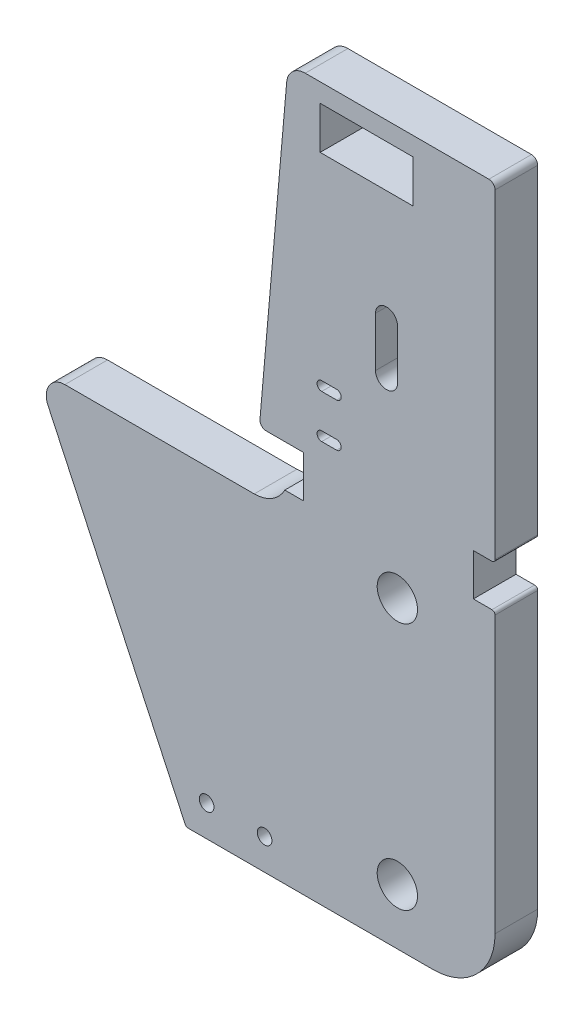
SolidWorks part; units mm, degrees
ref_plane "Front Plane" through (0, 0, 0) normal (0, 0, 1) x (1, 0, 0)
ref_plane "Top Plane" through (0, 0, 0) normal (0, 1, 0) x (1, 0, 0)
ref_plane "Right Plane" through (0, 0, 0) normal (1, 0, 0) x (0, 0, -1)
sketch "Sketch1" plane through (0, 0, 0) normal (0, 0, 1) x (1, 0, 0)
  line L0 (0, 0) -> (0, -53.098)
  line L1 (0, -53.098) -> (-3.5, -53.098)
  line L2 (-3.5, -53.098) -> (-3.5, -59.858)
  line L3 (-3.5, -59.858) -> (0, -59.858)
  line L4 (0, -59.858) -> (0, -114.858)
  line L5 (0, -114.858) -> (-49.8185, -114.858)
  line L6 (-49.8185, -114.858) -> (-74.0665, -62.858)
  line L7 (-33.3545, 0) -> (-38, -53.098)
  line L8 (-38, -53.098) -> (-30.9, -53.098)
  line L9 (-30.9, -53.098) -> (-30.9, -59.858)
  line L10 (-30.9, -59.858) -> (-33.9, -59.858)
  line L11 (-33.9, -59.858) -> (-33.9, -62.858)
  line L12 (-33.9, -62.858) -> (-74.0665, -62.858)
  line L13 (-33.3545, 0) -> (0, 0)
  dimension "D1" = 53.098
  dimension "D2" = 6.76
  dimension "D3" = 3.5
  dimension "D4" = 55
  dimension "D5" = 49.8185
  dimension "D6" = 57.3757
  dimension "D7" = 115
  dimension "D8" = 33.3545
  dimension "D9" = 7.1
  dimension "D10" = 95
  dimension "D11" = 3
  dimension "D12" = 3
extrude "Boss-Extrude1" add sketch "Sketch1" along normal blind 6.88 contours L13 L7 L8 L9 L10 L11 L12 L6 L5 L4 L3 L2 L1 L0
sketch "Sketch2" plane through (0, 0, 6.88) normal (0, 0, 1) x (1, 0, 0)
  line L0 (-33.3545, 0) -> (0, 0) construction
  line L1 (-13.2, -9.858) -> (-28.2, -9.858)
  line L2 (-13.2, -9.858) -> (-13.2, -3)
  line L3 (-13.2, -3) -> (-28.2, -3)
  line L4 (-28.2, -9.858) -> (-28.2, -3)
  line L5 (-13.2, -9.858) -> (-28.2, -3) construction
  line L6 (-13.2, -3) -> (-28.2, -9.858) construction
  line L7 (0, 0) -> (0, -53.098) construction
  point P0 (-20.7, -6.429)
  dimension "D1" = 15
  dimension "D2" = 6.858
  dimension "D3" = 3
  dimension "D4" = 13.2
extrude "Cut-Extrude1" cut sketch "Sketch2" against normal through all
sketch "Sketch3" plane through (0, 0, 6.88) normal (0, 0, 1) x (1, 0, 0)
  line L0 (0, -59.858) -> (0, -114.858) construction
  line L1 (0, -114.858) -> (-49.8185, -114.858) construction
  circle A0 centre (-15.75, -65.858) radius 3.25
  circle A1 centre (-15.75, -105.858) radius 3.25
  dimension "D1" = 6.5
  dimension "D2" = 15.75
  dimension "D3" = 40
  dimension "D4" = 9
extrude "Cut-Extrude2" cut sketch "Sketch3" against normal through all
sketch "Sketch4" plane through (0, 0, 6.88) normal (0, 0, 1) x (1, 0, 0)
  line L0 (0, -59.858) -> (0, -114.858) construction
  line L1 (0, -114.858) -> (-49.8185, -114.858) construction
  line L2 (-27.95, -49.358) -> (-25.55, -49.358) construction
  line L3 (-27.95, -48.608) -> (-25.55, -48.608)
  line L4 (-27.95, -50.108) -> (-25.55, -50.108)
  line L5 (-27.95, -42.358) -> (-25.55, -42.358) construction
  line L6 (-27.95, -41.608) -> (-25.55, -41.608)
  line L7 (-27.95, -43.108) -> (-25.55, -43.108)
  line L8 (-38, -53.098) -> (-30.9, -53.098) construction
  line L9 (0, 0) -> (0, -53.098) construction
  circle A0 centre (-46.5, -109.858) radius 1.1811
  circle A1 centre (-37.1528, -109.858) radius 1.1811
  arc A2 (-27.95, -48.608) -> (-27.95, -50.108) centre (-27.95, -49.358) ccw
  arc A3 (-25.55, -50.108) -> (-25.55, -48.608) centre (-25.55, -49.358) ccw
  arc A4 (-27.95, -41.608) -> (-27.95, -43.108) centre (-27.95, -42.358) ccw
  arc A5 (-25.55, -43.108) -> (-25.55, -41.608) centre (-25.55, -42.358) ccw
  point P10 (-26.75, -49.358)
  point P16 (-26.75, -42.358)
  dimension "D2" = 2.3622
  dimension "D9" = 0.75
  dimension "D1" = 9.3472
  dimension "D3" = 37.1528
  dimension "D4" = 5
  dimension "D5" = 2.4
  dimension "D6" = 3.74
  dimension "D7" = 7
  dimension "D8" = 25.55
extrude "Cut-Extrude3" cut sketch "Sketch4" against normal through all
sketch "Sketch5" plane through (0, 0, 6.88) normal (0, 0, 1) x (1, 0, 0)
  line L0 (-17.5, -27.858) -> (-17.5, -35.858) construction
  line L1 (-15.725, -27.858) -> (-15.725, -35.858)
  line L2 (-19.275, -27.858) -> (-19.275, -35.858)
  line L3 (0, 0) -> (0, -53.098) construction
  line L4 (-33.3545, 0) -> (0, 0) construction
  arc A0 (-15.725, -27.858) -> (-19.275, -27.858) centre (-17.5, -27.858) ccw
  arc A1 (-19.275, -35.858) -> (-15.725, -35.858) centre (-17.5, -35.858) ccw
  point P2 (-17.5, -31.858)
  dimension "D2" = 1.775
  dimension "D1" = 8
  dimension "D3" = 17.5
  dimension "D4" = 27.858
extrude "Cut-Extrude4" cut sketch "Sketch5" against normal through all
fillet "Fillet1" radius 10 1 edges at (0, -114.858, 3.44)
fillet "Fillet2" radius 3 2 edges at (-74.0665, -62.858, 3.44) (-33.3545, 0, 3.44)
fillet "Fillet3" radius 0.5 3 edges at (0, -53.098, 3.44) (0, -59.858, 3.44) (-49.8185, -114.858, 3.44)
fillet "Fillet4" radius 1 2 edges at (0, 0, 3.44) (-38, -53.098, 3.44)
fillet "Fillet5" radius 5.5512 1 edges at (-33.9, -62.858, 3.44)
